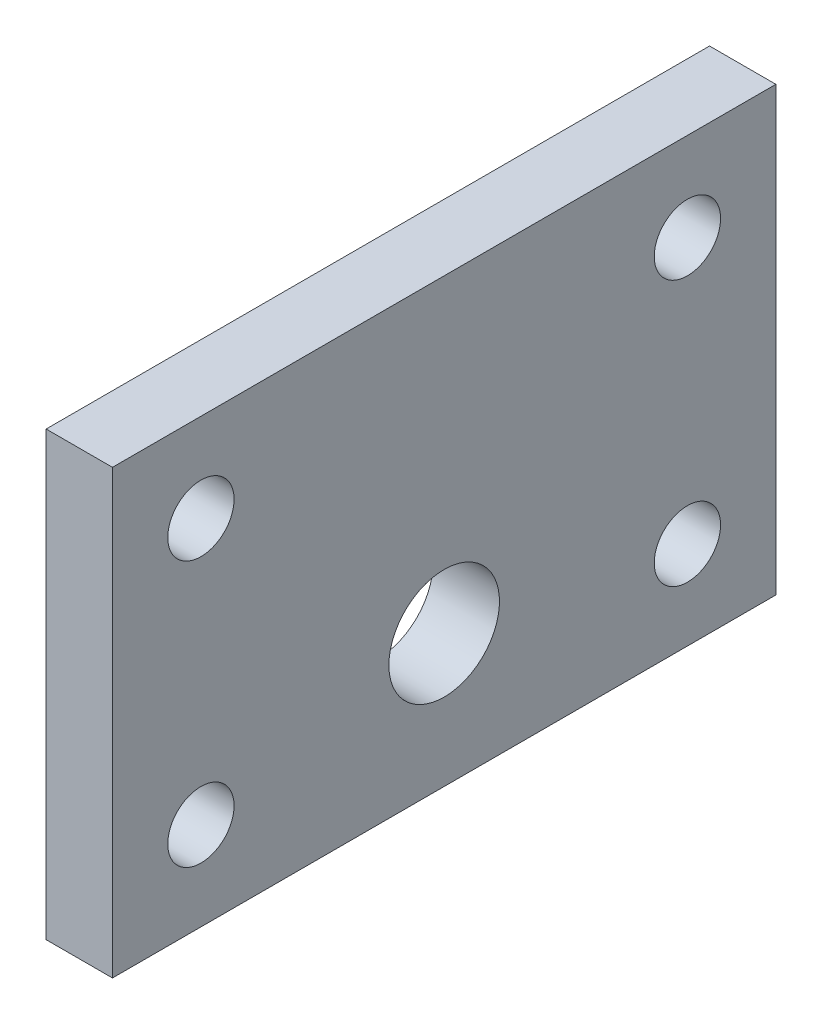
SolidWorks part; units mm, degrees
ref_plane "Front" through (0, 0, 0) normal (0, 0, 1) x (1, 0, 0)
ref_plane "Top" through (0, 0, 0) normal (0, 1, 0) x (1, 0, 0)
ref_plane "Right" through (0, 0, 0) normal (1, 0, 0) x (0, 0, -1)
sketch "草图1" plane through (0, 0, 0) normal (1, 0, 0) x (0, 0, -1)
  line L0 (-15, 0) -> (15, 0) construction
  line L1 (15, -10) -> (-15, -10)
  line L2 (15, -10) -> (15, 10)
  line L3 (15, 10) -> (-15, 10)
  line L4 (-15, -10) -> (-15, 10)
  line L5 (15, -10) -> (-15, 10) construction
  line L6 (15, 10) -> (-15, -10) construction
  circle A0 centre (0, 0) radius 3 construction
  circle A1 centre (-11, 6) radius 1.5
  circle A2 centre (-11, -6) radius 1.5
  circle A3 centre (11, -6) radius 1.5
  circle A4 centre (11, 6) radius 1.5
  point P0 (0, 0)
  dimension "D1" = 6
  dimension "D4" = 3
  dimension "D5" = 3
  dimension "D8" = 22
  dimension "D2" = 30
  dimension "D3" = 20
  dimension "D6" = 4
  dimension "D7" = 6
  dimension "D9" = 22
extrude "凸台-拉伸1" add sketch "草图1" along normal blind 3
sketch "草图2" plane through (0, 0, 0) normal (-1, 0, 0) x (0, 0, 1)
  line L0 (0, -10) -> (0, 10) construction
  line L1 (15, -10) -> (-15, -10) construction
  line L2 (-15, 10) -> (15, 10) construction
  circle A0 centre (0, -4) radius 2.5
  dimension "D1" = 5
  dimension "D2" = 14
extrude "切除-拉伸1" cut sketch "草图2" against normal up to next
